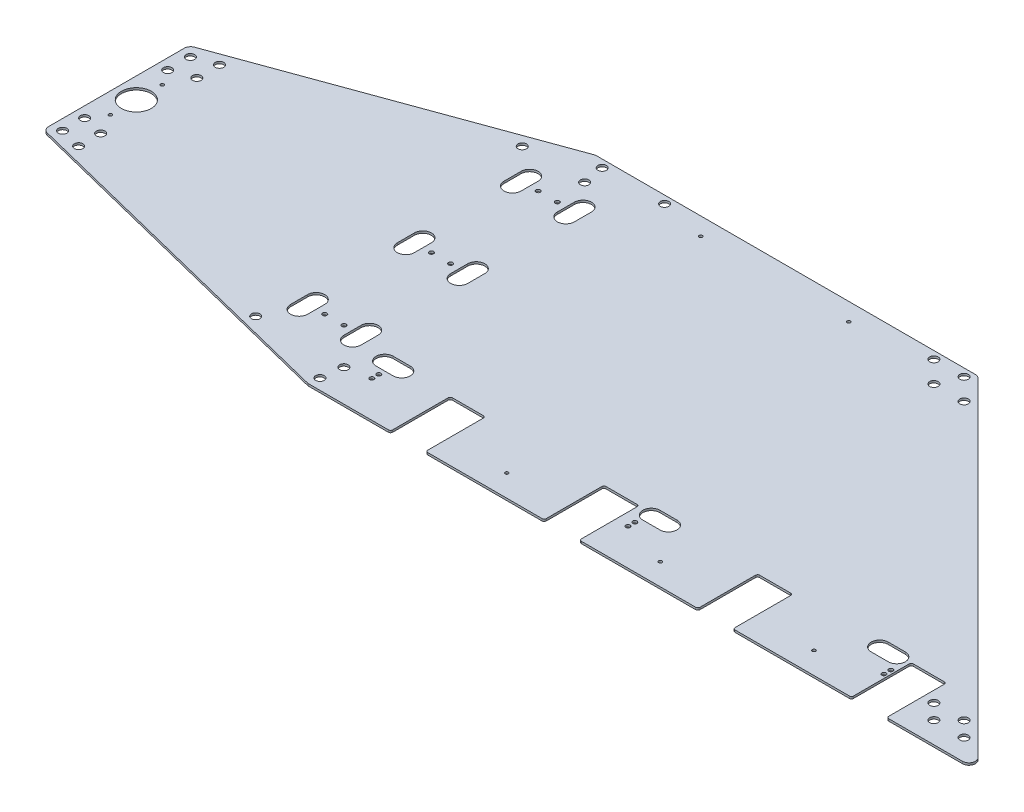
SolidWorks part; units mm, degrees
material "PC High Viscosity"
ref_plane "Front Plane" through (0, 0, 0) normal (0, 0, 1) x (1, 0, 0)
ref_plane "Top Plane" through (0, 0, 0) normal (0, 1, 0) x (1, 0, 0)
ref_plane "Right Plane" through (0, 0, 0) normal (1, 0, 0) x (0, 0, -1)
sketch "Sketch2" plane through (0, 0, 0) normal (0, 1, 0) x (1, 0, 0)
  line L5 (993.5568, 0) -> (0.4168, 0) construction
  line L6 (-516.6797, 128.8227) -> (-1.1348, 0.2829)
  line L7 (1.1695, 0) -> (973.9292, 0)
  line L8 (491.7144, 505.2102) -> (980.6644, 16.2602)
  line L9 (-78.5666, 508) -> (484.9792, 508)
  line L10 (-81.8243, 507.4256) -> (-517.6331, 348.8041)
  line L11 (-523.9004, 339.8536) -> (-523.9004, 138.0648)
  line L36 (122.8448, 0) -> (122.8448, 88.9)
  line L37 (122.8448, 88.9) -> (175.1688, 88.9)
  line L38 (175.1688, 0) -> (175.1688, 88.9)
  line L49 (351.4448, 0) -> (351.4448, 88.9)
  line L50 (351.4448, 88.9) -> (403.7688, 88.9)
  line L51 (403.7688, 0) -> (403.7688, 88.9)
  line L57 (580.0448, 0) -> (580.0448, 88.9)
  line L58 (580.0448, 88.9) -> (632.3688, 88.9)
  line L59 (632.3688, 0) -> (632.3688, 88.9)
  line L61 (808.6448, 0) -> (808.6448, 88.9)
  line L62 (808.6448, 88.9) -> (860.9688, 88.9)
  line L63 (860.9688, 0) -> (860.9688, 88.9)
  arc A0 (-517.6331, 348.8041) -> (-523.9004, 339.8536) centre (-514.3754, 339.8536) ccw
  arc A1 (-523.9004, 138.0648) -> (-516.6797, 128.8227) centre (-514.3754, 138.0648) ccw
  arc A2 (-1.1348, 0.2829) -> (1.1695, 0) centre (1.1695, 9.525) ccw
  arc A3 (980.6644, 16.2602) -> (973.9292, 0) centre (973.9292, 9.525) cw
  arc A4 (491.7144, 505.2102) -> (484.9792, 508) centre (484.9792, 498.475) ccw
  arc A5 (-81.8243, 507.4256) -> (-78.5666, 508) centre (-78.5666, 498.475) cw
  circle A6 centre (133.2169, 15.875) radius 7.62
  circle A7 centre (5.8746, 47.625) radius 6.35
  circle A8 centre (1.9762, 15.875) radius 6.35
  circle A9 centre (-125.3661, 47.625) radius 6.35
  circle A10 centre (-508.0254, 175.7547) radius 6.35
  circle A11 centre (-508.0254, 143.0327) radius 6.35
  circle A12 centre (-476.2754, 167.8385) radius 6.35
  circle A13 centre (-476.2754, 135.1165) radius 6.35
  circle A14 centre (-508.0254, 333.1213) radius 6.35
  circle A15 centre (-476.2754, 344.6773) radius 6.35
  circle A16 centre (-476.2754, 310.8897) radius 6.35
  circle A17 centre (-508.0254, 299.3336) radius 6.35
  circle A18 centre (-146.0386, 464.8731) radius 6.35
  circle A19 centre (-58.8062, 496.6231) radius 6.35
  circle A20 centre (-53.2079, 464.8731) radius 6.35
  circle A21 centre (34.0246, 496.6231) radius 6.35
  circle A22 centre (434.692, 496.623) radius 6.35
  circle A23 centre (466.4419, 464.873) radius 6.35
  circle A24 centre (479.5932, 496.623) radius 6.35
  circle A25 centre (511.3432, 464.873) radius 6.35
  circle A26 centre (877.3398, 53.975) radius 6.35
  circle A27 centre (922.2411, 53.975) radius 6.35
  circle A28 centre (899.5648, 31.75) radius 6.35
  circle A29 centre (944.4661, 31.75) radius 6.35
  circle A31 centre (322.9287, 481.637) radius 2.4575
  circle A32 centre (263.3068, 32.385) radius 2.4575
  circle A33 centre (491.9068, 32.385) radius 2.4575
  circle A34 centre (720.5068, 32.385) radius 2.4575
  circle A35 centre (-493.0394, 276.2907) radius 2.4574
  circle A36 centre (-493.0394, 199.0909) radius 2.4574
  circle A37 centre (102.7505, 481.637) radius 2.4575
  point P8 (-523.9004, 346.523)
  point P18 (-523.9004, 130.623)
  point P21 (0, 0)
  point P24 (996.9246, 0)
  dimension "D9" = 9.525
  dimension "D11" = 121.6753
  dimension "D12" = 52.324
  dimension "D13" = 176.276
  dimension "D14" = 176.276
  dimension "D15" = 176.276
  dimension "D16" = 220.1782
  dimension "D39" = 12.7
  dimension "D45" = 15.24
  dimension "D35" = 4.9149
  dimension "D51" = 4.9149
  dimension "D53" = 4.9149
  dimension "D1" = 523.9004
  dimension "D2" = 508
  dimension "D3" = 1520.825
  dimension "D4" = 166
  dimension "D5" = 160
  dimension "D6" = 110
  dimension "D7" = 215.9
  dimension "D8" = 45
  dimension "D10" = 531.3276
  dimension "D24" = 88.9
  dimension "D25" = 199.0909
  dimension "D29" = 77.1998
  dimension "D30" = 88.9
  dimension "D31" = 88.9
  dimension "D32" = 88.9
extrude "Boss-Extrude1" add sketch "Sketch2" along normal blind 3.175 contours A5 L10 A0 L11 A1 L6 A2 L7 A3 L8 A4 L9 region at (166.618, 0, -241.3361)
fillet "Fillet1" radius 3.175 16 edges at (175.1688, 1.5875, -88.9) (122.8448, 1.5875, -88.9) (351.4448, 1.5875, -88.9) (403.7688, 1.5875, -88.9) (632.3688, 1.5875, -88.9) (580.0448, 1.5875, -88.9) (860.9688, 1.5875, -88.9) (808.6448, 1.5875, -88.9) (632.3688, 1.5875, 0) (580.0448, 1.5875, 0) (403.7688, 1.5875, 0) (351.4448, 1.5875, 0) (175.1688, 1.5875, 0) (122.8448, 1.5875, 0) (860.9688, 1.5875, 0) (808.6448, 1.5875, 0)
sketch "Sketch6" plane through (0, 3.175, 0) normal (0, 1, 0) x (1, 0, 0)
  line L0 (-22.6592, 431.8127) -> (-22.6592, 406.4127) construction
  line L1 (-9.9592, 431.8127) -> (-9.9592, 406.4127)
  line L2 (-35.3592, 431.8127) -> (-35.3592, 406.4127)
  line L3 (-102.0342, 431.8127) -> (-102.0342, 406.4127) construction
  line L4 (-89.3342, 431.8127) -> (-89.3342, 406.4127)
  line L5 (-114.7342, 431.8127) -> (-114.7342, 406.4127)
  line L6 (-22.6592, 273.0627) -> (-22.6592, 247.6627) construction
  line L7 (-9.9592, 273.0627) -> (-9.9592, 247.6627)
  line L8 (-35.3592, 273.0627) -> (-35.3592, 247.6627)
  line L9 (-102.0342, 273.0627) -> (-102.0342, 247.6627) construction
  line L10 (-89.3342, 273.0627) -> (-89.3342, 247.6627)
  line L11 (-114.7342, 273.0627) -> (-114.7342, 247.6627)
  line L12 (-22.6592, 114.3127) -> (-22.6592, 88.9127) construction
  line L13 (-9.9592, 114.3127) -> (-9.9592, 88.9127)
  line L14 (-35.3592, 114.3127) -> (-35.3592, 88.9127)
  line L15 (-102.0342, 114.3127) -> (-102.0342, 88.9127) construction
  line L16 (-89.3342, 114.3127) -> (-89.3342, 88.9127)
  line L17 (-114.7342, 114.3127) -> (-114.7342, 88.9127)
  arc A0 (-9.9592, 431.8127) -> (-35.3592, 431.8127) centre (-22.6592, 431.8127) ccw
  arc A1 (-35.3592, 406.4127) -> (-9.9592, 406.4127) centre (-22.6592, 406.4127) ccw
  arc A2 (-89.3342, 431.8127) -> (-114.7342, 431.8127) centre (-102.0342, 431.8127) ccw
  arc A3 (-114.7342, 406.4127) -> (-89.3342, 406.4127) centre (-102.0342, 406.4127) ccw
  arc A4 (-9.9592, 273.0627) -> (-35.3592, 273.0627) centre (-22.6592, 273.0627) ccw
  arc A5 (-35.3592, 247.6627) -> (-9.9592, 247.6627) centre (-22.6592, 247.6627) ccw
  arc A6 (-89.3342, 273.0627) -> (-114.7342, 273.0627) centre (-102.0342, 273.0627) ccw
  arc A7 (-114.7342, 247.6627) -> (-89.3342, 247.6627) centre (-102.0342, 247.6627) ccw
  arc A8 (-9.9592, 114.3127) -> (-35.3592, 114.3127) centre (-22.6592, 114.3127) ccw
  arc A9 (-35.3592, 88.9127) -> (-9.9592, 88.9127) centre (-22.6592, 88.9127) ccw
  arc A10 (-89.3342, 114.3127) -> (-114.7342, 114.3127) centre (-102.0342, 114.3127) ccw
  arc A11 (-114.7342, 88.9127) -> (-89.3342, 88.9127) centre (-102.0342, 88.9127) ccw
  point P1 (-76.6342, 419.1127)
  point P2 (-48.0592, 260.3627)
  point P3 (-76.6342, 260.3627)
  point P4 (-76.6342, 101.6127)
  point P5 (-48.0592, 101.6127)
  point P6 (-48.0592, 419.1127)
  point P8 (-22.6592, 419.1127)
  point P13 (-102.0342, 419.1127)
  point P24 (-22.6592, 260.3627)
  point P31 (-102.0342, 260.3627)
  point P38 (-22.6592, 101.6127)
  point P45 (-102.0342, 101.6127)
  dimension "D1" = 25.4
  dimension "D2" = 25.4
  dimension "D3" = 12.7
  dimension "D5" = 12.7
extrude "Cut-Extrude1" cut sketch "Sketch6" against normal blind 6.35
hole_wizard "1/4 (0.25) Diameter Hole1" positions "3DSketch1" profile "Sketch7" hole size "1/4" standard "ANSI Inch" end condition through all
sketch3d "3DSketch1"
  point P0 (-48.0592, 3.175, -419.1127)
  point P3 (-76.6342, 3.175, -419.1127)
  point P6 (-76.6342, 3.175, -260.3627)
  point P9 (-48.0592, 3.175, -260.3627)
  point P12 (-48.0592, 3.175, -101.6127)
  point P15 (-76.6342, 3.175, -101.6127)
sketch "Sketch7" plane through (-48.0592, 3.175, -419.1127) normal (1, 0, 0) x (0, 0, 1)
  line L0 (0, 0) -> (0, 3.175)
  line L1 (0, 3.175) -> (3.175, 3.175)
  line L2 (3.175, 3.175) -> (3.175, 0)
  line L5 (3.175, 0) -> (0, 0)
  line L11 (0, -6.35) -> (0, 107.95) construction
  dimension "Thru Hole Dia." = 6.35
  dimension "Thru Hole Depth" = 3.175
sketch "Sketch8" plane through (0, 3.175, 0) normal (0, 1, 0) x (1, 0, 0)
  line L0 (-493.0394, 276.2907) -> (-493.0394, 199.0909) construction
  circle A0 centre (-493.0394, 237.6908) radius 22.225
  point P0 (-493.0394, 237.6908)
  dimension "D1" = 44.45
extrude "Cut-Extrude2" cut sketch "Sketch8" against normal through all
sketch "Sketch9" plane through (0, 3.175, 0) normal (0, 1, 0) x (1, 0, 0)
  line L0 (1.1695, 0) -> (119.6698, 0) construction
  line L1 (122.8448, 3.175) -> (122.8448, 85.725) construction
  line L2 (403.7688, 3.175) -> (403.7688, 85.725) construction
  line L3 (808.6448, 3.175) -> (808.6448, 85.725) construction
  point P0 (41.0568, 53.975)
  point P1 (422.0568, 53.975)
  point P2 (803.0568, 53.975)
  dimension "D1" = 53.975
  dimension "D2" = 81.788
  dimension "D3" = 18.288
  dimension "D4" = 5.588
hole_wizard "1/4 (0.25) Diameter Hole2" positions "Sketch10" profile "Sketch11" hole size "1/4" standard "ANSI Inch" end condition through all
sketch "Sketch10" plane through (0, 3.175, 0) normal (0, 1, 0) x (1, 0, 0)
  point P0 (41.0568, 53.975)
  point P3 (422.0568, 53.975)
  point P6 (803.0568, 53.975)
  point P10 (41.0568, 64.2938)
  point P12 (422.0568, 64.2938)
  point P14 (803.0568, 64.2938)
  dimension "D1" = 10.3187
sketch "Sketch11" plane through (41.0568, 3.175, -53.975) normal (1, 0, 0) x (0, 0, 1)
  line L0 (0, 0) -> (0, 3.175)
  line L1 (0, 3.175) -> (3.175, 3.175)
  line L2 (3.175, 3.175) -> (3.175, 0)
  line L5 (3.175, 0) -> (0, 0)
  line L11 (0, -6.35) -> (0, 107.95) construction
  dimension "Thru Hole Dia." = 6.35
  dimension "Thru Hole Depth" = 3.175
sketch "Sketch12" plane through (0, 3.175, 0) normal (0, 1, 0) x (1, 0, 0)
  line L0 (28.3568, 85.725) -> (53.7568, 85.725) construction
  line L1 (28.3568, 98.425) -> (53.7568, 98.425)
  line L2 (28.3568, 73.025) -> (53.7568, 73.025)
  line L3 (425.2318, 85.725) -> (450.6318, 85.725) construction
  line L4 (425.2318, 98.425) -> (450.6318, 98.425)
  line L5 (425.2318, 73.025) -> (450.6318, 73.025)
  line L6 (764.9568, 85.725) -> (790.3568, 85.725) construction
  line L7 (764.9568, 98.425) -> (790.3568, 98.425)
  line L8 (764.9568, 73.025) -> (790.3568, 73.025)
  arc A0 (28.3568, 98.425) -> (28.3568, 73.025) centre (28.3568, 85.725) ccw
  arc A1 (53.7568, 73.025) -> (53.7568, 98.425) centre (53.7568, 85.725) ccw
  arc A2 (425.2318, 98.425) -> (425.2318, 73.025) centre (425.2318, 85.725) ccw
  arc A3 (450.6318, 73.025) -> (450.6318, 98.425) centre (450.6318, 85.725) ccw
  arc A4 (764.9568, 98.425) -> (764.9568, 73.025) centre (764.9568, 85.725) ccw
  arc A5 (790.3568, 73.025) -> (790.3568, 98.425) centre (790.3568, 85.725) ccw
  circle A6 centre (720.5068, 32.385) radius 2.4575 construction
  circle A7 centre (491.9068, 32.385) radius 2.4575 construction
  circle A8 centre (263.3068, 32.385) radius 2.4575 construction
  circle A9 centre (720.5068, 32.385) radius 2.4575
  circle A10 centre (491.9068, 32.385) radius 2.4575
  circle A11 centre (263.3068, 32.385) radius 2.4575
  circle A12 centre (41.0568, 53.975) radius 3.175 construction
  circle A13 centre (422.0568, 53.975) radius 3.175 construction
  circle A14 centre (803.0568, 53.975) radius 3.175 construction
  circle A15 centre (41.0568, 53.975) radius 3.175
  circle A16 centre (422.0568, 53.975) radius 3.175
  circle A17 centre (803.0568, 53.975) radius 3.175
  point P2 (41.0568, 85.725)
  point P7 (437.9318, 85.725)
  point P14 (777.6568, 85.725)
  dimension "D1" = 12.7
  dimension "D2" = 25.4
  dimension "D3" = 31.75
  dimension "D4" = 12.7
  dimension "D5" = 3.175
extrude "Cut-Extrude3" cut sketch "Sketch12" against normal through all
